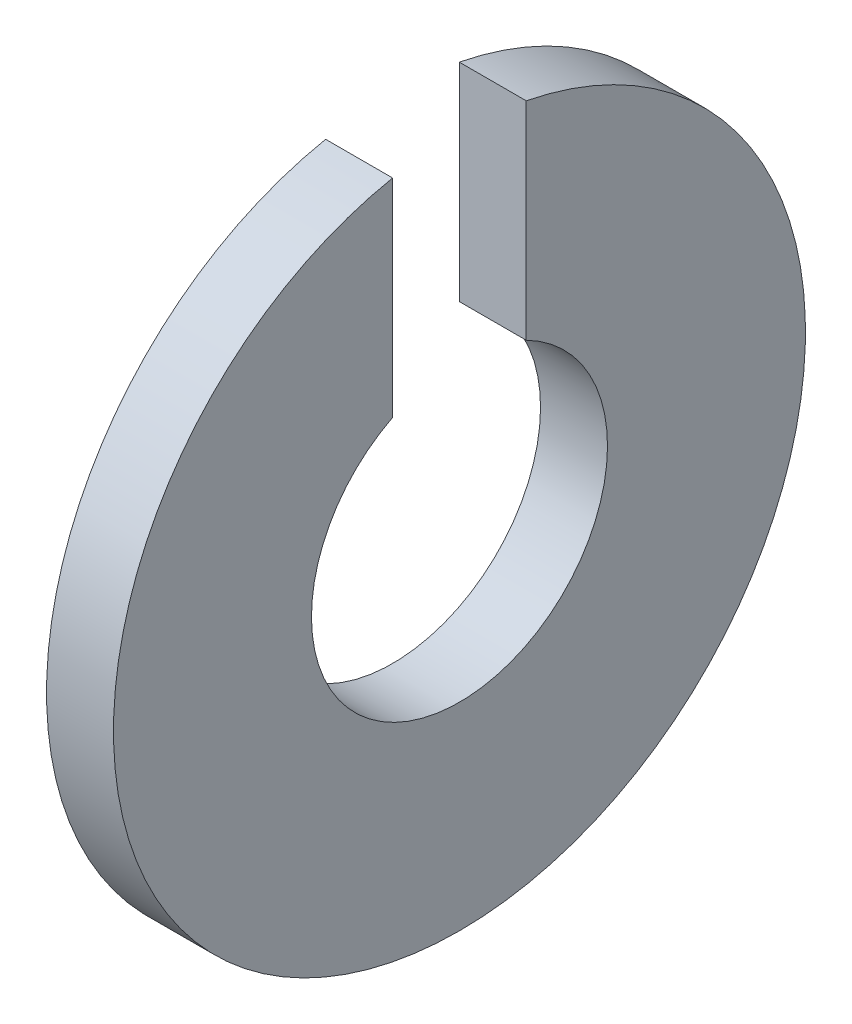
SolidWorks part; units mm, degrees
ref_plane "Front Plane" through (0, 0, 0) normal (0, 0, 1) x (1, 0, 0)
ref_plane "Top Plane" through (0, 0, 0) normal (0, 1, 0) x (1, 0, 0)
ref_plane "Right Plane" through (0, 0, 0) normal (1, 0, 0) x (0, 0, -1)
sketch "Sketch1" plane through (0, 0, 0) normal (1, 0, 0) x (0, 0, -1)
  line L2 (0.7596, 3.863) -> (0.7596, 1.5033)
  line L4 (-0.7609, 3.8628) -> (-0.7609, 1.5026)
  arc A0 (-0.7609, 1.5026) -> (0.7596, 1.5033) centre (0, 0) ccw
  arc A1 (-0.7609, 3.8628) -> (0.7596, 3.863) centre (0, 0) ccw
  point P4 (0, 2.8539)
extrude "Boss-Extrude1" add sketch "Sketch1" along normal blind 0.762
